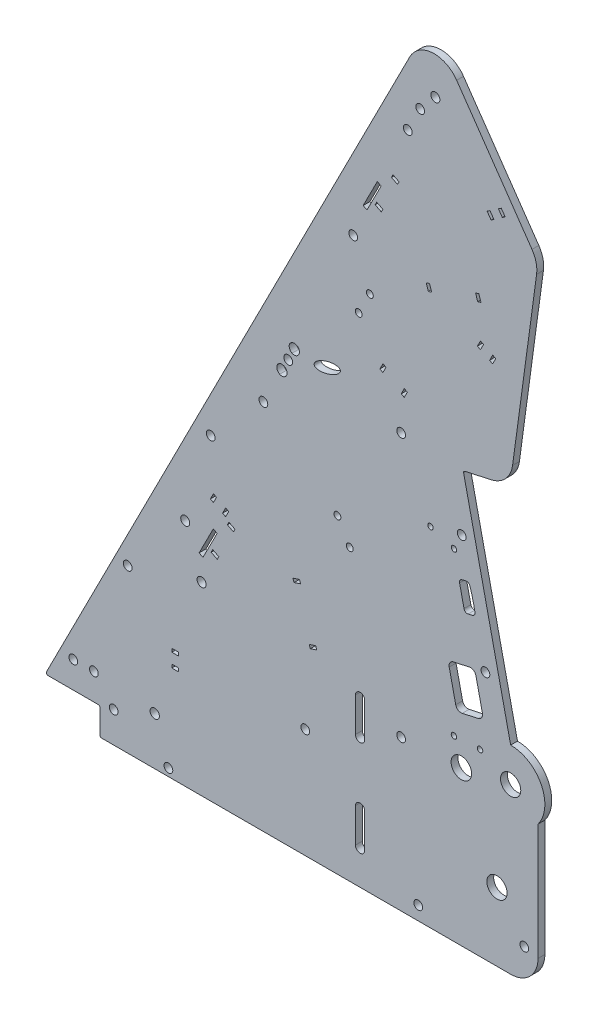
SolidWorks part; units mm, degrees
other "Markup1"
sketch "Sketch5"
ref_plane "Front Plane" through (0, 0, 0) normal (0, 0, 1) x (1, 0, 0)
ref_plane "Top Plane" through (0, 0, 0) normal (0, 1, 0) x (1, 0, 0)
ref_plane "Right Plane" through (0, 0, 0) normal (1, 0, 0) x (0, 0, -1)
sketch "Sketch1" plane through (0, 0, 0) normal (0, 0, 1) x (1, 0, 0)
  line L1 (228.6, -12.7) -> (228.6, 53.975)
  line L2 (178.7547, 351.4131) -> (0, 0)
  line L3 (228.6, 279.4) -> (178.7547, 351.4131)
  line L5 (0, 0) -> (25.4, 0)
  line L6 (25.4, 0) -> (25.4, -12.7)
  line L7 (25.4, -12.7) -> (228.6, -12.7)
  line L9 (215.9, 79.375) -> (193.9097, 178.5667)
  line L10 (193.9097, 178.5667) -> (215.6079, 183.377)
  line L11 (215.6079, 183.377) -> (228.6, 279.4)
  arc A0 (228.6, 53.975) -> (215.9, 79.375) centre (215.9, 63.5) ccw
  dimension "D7" = 12.7
  dimension "D8" = 76.2
  dimension "D10" = 31.75
  dimension "D2" = 292.1
  dimension "D3" = 25.4
  dimension "D4" = 215.9
  dimension "D5" = 394.2644
  dimension "D6" = 203.2
  dimension "D9" = 63.039
  dimension "D11" = 101.6
  dimension "D12" = 12.5
  dimension "D13" = 22.225
extrude "Boss-Extrude1" add sketch "Sketch1" along normal blind 3.175
sketch "Sketch2" plane through (0, 0, 3.175) normal (0, 0, 1) x (1, 0, 0)
  line L0 (178.7547, 351.4131) -> (0, 0) construction
  line L1 (25.4, -12.7) -> (228.6, -12.7) construction
  line L2 (215.9, 79.375) -> (193.9097, 178.5667) construction
  line L3 (193.9097, 178.5667) -> (215.6079, 183.377) construction
  line L4 (215.9, 79.375) -> (193.9097, 178.5667) construction
  line L5 (64.9432, 94.0578) -> (72.5445, 73.1732) construction
  line L6 (64.9432, 94.0578) -> (89.8317, 94.0578) construction
  line L10 (228.6, -12.7) -> (228.6, 53.975) construction
  circle A0 centre (64.9432, 94.0578) radius 2.0955
  circle A1 centre (180.975, 322.1643) radius 2.0955
  circle A2 centre (72.5445, 73.1732) radius 2.0955
  circle A3 centre (193.2078, 152.3944) radius 2.032
  circle A4 centre (215.9, 63.5) radius 4.699
  circle A7 centre (173.0375, -6.35) radius 2.032
  circle A8 centre (204.203, 102.7985) radius 2.032
  circle A26 centre (209.55, 19.05) radius 4.699
  arc A30 (228.6, 53.975) -> (215.9, 79.375) centre (215.9, 63.5) ccw construction
  circle A31 centre (165.1, 179.3875) radius 2.032
  dimension "D3" = 4.191
  dimension "D5" = 4.191
  dimension "D9" = 4.191
  dimension "D20" = 9.398
  dimension "D23" = 9.398
  dimension "D18" = 4.064
  dimension "D26" = 4.064
  dimension "D14" = 4.064
  dimension "D2" = 15.24
  dimension "D6" = 15.24
  dimension "D7" = 22.225
  dimension "D21" = 44.45
  dimension "D22" = 6.35
  dimension "D19" = 160.3375
  dimension "D24" = 44.45
  dimension "D25" = 6.35
  dimension "D27" = 25.4
  dimension "D28" = 50.8
  dimension "D29" = 6.35
  dimension "D17" = 6.35
  dimension "D33" = 55.5625
  dimension "D15" = 114.3
  dimension "D4" = 180.975
  dimension "D8" = 70
extrude "Cut-Extrude1" cut sketch "Sketch2" against normal through all
sketch "Sketch7" plane through (0, 0, 3.175) normal (0, 0, 1) x (1, 0, 0)
  line L0 (146.05, 3.175) -> (146.05, 19.05) construction
  line L1 (143.891, 3.175) -> (143.891, 19.05)
  line L2 (148.209, 3.175) -> (148.209, 19.05)
  line L3 (146.05, 47.625) -> (146.05, 63.5) construction
  line L4 (143.891, 47.625) -> (143.891, 63.5)
  line L5 (148.209, 47.625) -> (148.209, 63.5)
  line L6 (25.4, -12.7) -> (228.6, -12.7) construction
  line L12 (228.6, -12.7) -> (228.6, 53.975) construction
  line L13 (25.4, -12.7) -> (228.6, -12.7) construction
  arc A0 (143.891, 3.175) -> (148.209, 3.175) centre (146.05, 3.175) ccw
  arc A1 (148.209, 19.05) -> (143.891, 19.05) centre (146.05, 19.05) ccw
  arc A2 (143.891, 47.625) -> (148.209, 47.625) centre (146.05, 47.625) ccw
  arc A3 (148.209, 63.5) -> (143.891, 63.5) centre (146.05, 63.5) ccw
  circle A8 centre (50.8, 9.525) radius 2.159
  point P2 (146.05, 11.1125)
  point P9 (146.05, 55.5625)
  dimension "D1" = 4.318
  dimension "D5" = 4.318
  dimension "D2" = 15.875
  dimension "D3" = 15.875
  dimension "D4" = 44.45
  dimension "D6" = 95.25
  dimension "D7" = 82.55
  dimension "D8" = 15.875
  dimension "D9" = 22.225
extrude "Cut-Extrude2" cut sketch "Sketch7" against normal through all
sketch "Sketch10" plane through (0, 0, 3.175) normal (0, 0, 1) x (1, 0, 0)
  circle A1 centre (165.1, 57.15) radius 2.032
  circle A2 centre (120.65, 38.1) radius 2.032
  circle A3 centre (13.0465, 12.3347) radius 2.032
  circle A4 centre (22.5715, 12.3347) radius 2.032
  circle A5 centre (38.2611, 62.6146) radius 2.032
  dimension "D1" = 4.064
  dimension "D2" = 4.064
  dimension "D4" = 63.5
  dimension "D5" = 69.85
extrude "Cut-Extrude3" cut sketch "Sketch10" against normal up to next
fillet "Fillet1" radius 12.7 4 edges at (228.6, -12.7, 1.5875) (178.7547, 351.4131, 1.5875) (215.6079, 183.377, 1.5875) (228.6, 279.4, 1.5875)
fillet "Fillet2" radius 0.7937 4 edges at (25.4, -12.7, 1.5875) (25.4, 0, 1.5875) (193.9097, 178.5667, 1.5875) (0, 0, 1.5875)
sketch "Sketch12" plane through (0, 0, 3.175) normal (0, 0, 1) x (1, 0, 0)
  circle A0 centre (31.75, 1.5875) radius 2.032
  circle A1 centre (222.25, 1.5875) radius 2.032
  circle A2 centre (57.15, -9.2075) radius 2.032
  circle A3 centre (57.15, -9.2075) radius 2.286 construction
  dimension "D1" = 4.064
  dimension "D2" = 4.064
extrude "Cut-Extrude5" cut sketch "Sketch12" against normal through all
sketch "Sketch13" plane through (0, 0, 3.175) normal (0, 0, 1) x (1, 0, 0)
  line L2 (194.6847, 178.7385) -> (206.9592, 181.4597) construction
  line L5 (199.2434, 101.699) -> (189.6226, 145.0954) construction
  line L6 (189.6022, 69.9806) -> (201.7089, 70.5092) construction
  line L7 (186.8444, 98.9502) -> (199.2434, 101.699)
  line L8 (186.8444, 98.9502) -> (190.9676, 80.3518)
  line L9 (190.9676, 80.3518) -> (203.3665, 83.1006)
  line L10 (199.2434, 101.699) -> (203.3665, 83.1006)
  line L11 (189.6022, 69.9806) -> (190.9676, 80.3518) construction
  line L12 (201.7089, 70.5092) -> (203.3665, 83.1006) construction
  line L13 (215.9, 79.375) -> (194.0815, 177.7917) construction
  line L14 (178.7216, 148.5324) -> (189.6226, 145.0954) construction
  line L15 (195.1281, 134.9336) -> (193.4153, 134.5539)
  line L16 (192.209, 132.6604) -> (194.2706, 123.3612)
  line L17 (196.1641, 122.1549) -> (198.1091, 122.5861)
  line L18 (211.4332, 99.5233) -> (205.2337, 98.1489) construction
  line L19 (198.3765, 158.4184) -> (211.4332, 99.5233) construction
  circle A0 centre (189.6022, 69.9806) radius 1.27
  circle A1 centre (201.7089, 70.5092) radius 1.27
  circle A2 centre (178.7216, 148.5324) radius 1.27
  circle A3 centre (189.6226, 145.0954) radius 1.27
  arc A4 (199.3306, 124.402) -> (196.9796, 133.88) centre (134.9024, 113.4517) ccw
  arc A6 (199.4957, 103.5221) -> (189.2475, 149.7492) centre (134.9024, 113.4517) ccw construction
  arc A7 (195.1281, 134.9336) -> (196.9796, 133.88) centre (195.4717, 133.3837) cw
  arc A8 (198.1091, 122.5861) -> (199.3306, 124.402) centre (197.7655, 124.136) ccw
  arc A9 (194.2706, 123.3612) -> (196.1641, 122.1549) centre (195.8205, 123.7048) ccw
  arc A10 (193.4153, 134.5539) -> (192.209, 132.6604) centre (193.7589, 133.004) ccw
  point P26 (208.3335, 98.8361)
  point P31 (196.515, 135.2411)
  point P36 (194.6142, 121.8113)
  point P39 (191.8654, 134.2103)
  dimension "D7" = 2.54
  dimension "D16" = 1.5875
  dimension "D2" = 11.43
  dimension "D3" = 76.2
  dimension "D4" = 12.7
  dimension "D5" = 19.05
  dimension "D6" = 120
  dimension "D8" = 110
  dimension "D9" = 80
  dimension "D10" = 12.7
  dimension "D11" = 44.45
  dimension "D12" = 11.43
  dimension "D13" = 12.7
  dimension "D14" = 4.7625
  dimension "D15" = 38.1
extrude "Cut-Extrude6" cut sketch "Sketch13" against normal through all both and the other way through all
sketch "Sketch14" plane through (0, 0, 3.175) normal (0, 0, 1) x (1, 0, 0)
  line L0 (26.1937, -12.7) -> (215.9, -12.7) construction
  line L1 (228.6, 0) -> (228.6, 53.975) construction
  line L2 (112.7125, 182.5625) -> (101.1964, 159.9231) construction
  line L3 (169.1053, 332.4434) -> (0.5868, 1.1536) construction
  line L4 (112.7125, 182.5625) -> (136.864, 190.4279) construction
  line L5 (147.4827, 261.9243) -> (154.0469, 274.8287)
  line L6 (147.4827, 261.9243) -> (149.2654, 261.0175)
  line L7 (154.0469, 274.8287) -> (155.8295, 273.922)
  line L8 (149.2654, 261.0175) -> (155.8295, 273.922)
  line L9 (169.1053, 332.4434) -> (0.5868, 1.1536) construction
  line L10 (160.5905, 279.7801) -> (161.3102, 281.1951)
  line L11 (160.5905, 279.7801) -> (163.4204, 278.3406)
  line L12 (161.3102, 281.1951) -> (164.1402, 279.7556)
  line L13 (163.4204, 278.3406) -> (164.1402, 279.7556)
  line L14 (153.7897, 266.4104) -> (156.6196, 264.9709)
  line L15 (153.7897, 266.4104) -> (153.0699, 264.9954)
  line L16 (156.6196, 264.9709) -> (155.8998, 263.5559)
  line L17 (153.0699, 264.9954) -> (155.8998, 263.5559)
  line L19 (178.2697, 245.9923) -> (179.2404, 242.9693)
  line L20 (178.2697, 245.9923) -> (176.7582, 245.5069)
  line L21 (179.2404, 242.9693) -> (177.7289, 242.4839)
  line L22 (176.7582, 245.5069) -> (177.7289, 242.4839)
  line L24 (200.6096, 249.8308) -> (199.639, 252.8538)
  line L25 (200.6096, 249.8308) -> (202.1211, 250.3161)
  line L26 (199.639, 252.8538) -> (201.1505, 253.3391)
  line L27 (202.1211, 250.3161) -> (201.1505, 253.3391)
  line L34 (77.9534, 97.2255) -> (79.736, 96.3187)
  line L47 (77.9534, 97.2255) -> (71.3892, 84.3211)
  line L56 (79.736, 96.3187) -> (73.1718, 83.4143)
  line L57 (71.3892, 84.3211) -> (73.1718, 83.4143)
  line L58 (85.2167, 103.5918) -> (84.497, 102.1769)
  line L59 (85.2167, 103.5918) -> (88.0466, 102.1523)
  line L60 (84.497, 102.1769) -> (87.3269, 100.7374)
  line L61 (88.0466, 102.1523) -> (87.3269, 100.7374)
  line L62 (156.643, 199.3999) -> (158.0826, 202.2298)
  line L63 (156.643, 199.3999) -> (155.2281, 200.1197)
  line L64 (158.0826, 202.2298) -> (156.6676, 202.9496)
  line L65 (155.2281, 200.1197) -> (156.6676, 202.9496)
  line L66 (165.1328, 195.0814) -> (166.5723, 197.9113)
  line L67 (165.1328, 195.0814) -> (166.5478, 194.3617)
  line L68 (166.5723, 197.9113) -> (167.9873, 197.1916)
  line L69 (166.5478, 194.3617) -> (167.9873, 197.1916)
  line L78 (77.6961, 88.8072) -> (76.9764, 87.3922)
  line L79 (201.9154, 234.7497) -> (200.4759, 231.9198)
  line L80 (201.9154, 234.7497) -> (203.3303, 234.0299)
  line L81 (200.4759, 231.9198) -> (201.8908, 231.2)
  line L82 (203.3303, 234.0299) -> (201.8908, 231.2)
  line L83 (206.1357, 229.0407) -> (207.5752, 231.8707)
  line L84 (206.1357, 229.0407) -> (207.5507, 228.321)
  line L85 (207.5752, 231.8707) -> (208.9902, 231.1509)
  line L86 (207.5507, 228.321) -> (208.9902, 231.1509)
  line L88 (205.014, 288.3715) -> (206.821, 285.7609)
  line L89 (205.014, 288.3715) -> (206.3193, 289.275)
  line L90 (206.821, 285.7609) -> (208.1263, 286.6644)
  line L91 (206.3193, 289.275) -> (208.1263, 286.6644)
  line L92 (210.2352, 291.9855) -> (212.0422, 289.3749)
  line L93 (210.2352, 291.9855) -> (211.5405, 292.889)
  line L94 (212.0422, 289.3749) -> (213.3475, 290.2784)
  line L95 (211.5405, 292.889) -> (213.3475, 290.2784)
  line L96 (225.7968, 283.4499) -> (190.8675, 333.9133) construction
  line L97 (77.6961, 88.8072) -> (80.5261, 87.3677)
  line L98 (76.9764, 87.3922) -> (79.8063, 85.9527)
  line L99 (80.5261, 87.3677) -> (79.8063, 85.9527)
  line L100 (122.4534, 73.1037) -> (122.9512, 71.5963)
  line L101 (122.4534, 73.1037) -> (125.4682, 74.0993)
  line L102 (122.9512, 71.5963) -> (125.9661, 72.5919)
  line L103 (125.4682, 74.0993) -> (125.9661, 72.5919)
  line L104 (114.9173, 95.9228) -> (115.4151, 94.4154)
  line L105 (114.9173, 95.9228) -> (117.9322, 96.9185)
  line L106 (115.4151, 94.4154) -> (118.43, 95.411)
  line L107 (117.9322, 96.9185) -> (118.43, 95.411)
  line L108 (73.3338, 88.1438) -> (77.899, 97.1186) construction
  line L109 (75.1164, 87.2371) -> (79.6816, 96.2118) construction
  line L110 (76.2812, 89.5269) -> (86.5313, 84.313) construction
  line L111 (83.082, 102.8966) -> (93.3321, 97.6827) construction
  line L112 (121.934, 72.0825) -> (123.4755, 75.113) construction
  line L113 (127.9171, 72.8537) -> (123.4755, 75.113) construction
  line L114 (112.3753, 83.5081) -> (119.5388, 97.5909) construction
  line L115 (112.1491, 96.0767) -> (117.4079, 93.4017) construction
  line L116 (149.0052, 264.9173) -> (147.5544, 262.0651) construction
  line L117 (150.7878, 264.0106) -> (151.2099, 264.8403) construction
  line L118 (162.6248, 261.9162) -> (152.3747, 267.1302) construction
  line L119 (169.4256, 275.2859) -> (159.1755, 280.4999) construction
  line L120 (199.3876, 252.3597) -> (200.1584, 253.8749) construction
  line L121 (198.6169, 250.8445) -> (203.0585, 248.5852) construction
  line L122 (203.2698, 247.9167) -> (195.3067, 232.262) construction
  line L123 (180.2625, 244.9786) -> (175.0037, 247.6536) construction
  line L124 (178.1316, 240.7894) -> (185.2951, 254.8722) construction
  line L125 (190.7763, 226.1672) -> (185.5176, 228.8422) construction
  line L126 (58.7375, 39.6875) -> (61.9125, 39.6875)
  line L127 (58.7375, 39.6875) -> (58.7375, 38.1)
  line L128 (61.9125, 39.6875) -> (61.9125, 38.1)
  line L129 (58.7375, 38.1) -> (61.9125, 38.1)
  line L130 (58.7375, 33.3375) -> (61.9125, 33.3375)
  line L131 (58.7375, 33.3375) -> (58.7375, 31.75)
  line L132 (61.9125, 33.3375) -> (61.9125, 31.75)
  line L133 (58.7375, 31.75) -> (61.9125, 31.75)
  line L135 (78.0516, 111.4242) -> (76.6121, 108.5943)
  line L136 (78.0516, 111.4242) -> (79.4665, 110.7045)
  line L137 (76.6121, 108.5943) -> (78.027, 107.8745)
  line L138 (79.4665, 110.7045) -> (78.027, 107.8745)
  line L139 (82.2719, 105.7153) -> (83.7114, 108.5452)
  line L140 (82.2719, 105.7153) -> (83.6869, 104.9955)
  line L141 (83.7114, 108.5452) -> (85.1264, 107.8254)
  line L142 (83.6869, 104.9955) -> (85.1264, 107.8254)
  circle A0 centre (142.875, 247.65) radius 2.032
  circle A1 centre (112.7125, 182.5625) radius 2.032
  circle A2 centre (101.1964, 159.9231) radius 2.032
  circle A3 centre (150.594, 227.8985) radius 1.6 construction
  circle A4 centre (145.4254, 217.7376) radius 1.6 construction
  circle A5 centre (135.5457, 131.3585) radius 1.6 construction
  circle A6 centre (141.2457, 121.4859) radius 1.6 construction
  circle A7 centre (150.594, 227.8985) radius 1.6
  circle A8 centre (145.4254, 217.7376) radius 1.6
  circle A9 centre (135.5457, 131.3585) radius 1.6
  circle A10 centre (141.2457, 121.4859) radius 1.6
  arc A13 (0, 1.5875) -> (1.5875, 0) centre (1.5875, 1.5875) ccw construction
  ellipse E0 centre (109.8335, 176.9027) end of major axis (108.7539, 174.7802) minor radius 2.32 (108.7539, 174.7802) -> (110.9131, 179.0251) ccw construction
  ellipse E1 centre (109.8335, 176.9027) end of major axis (108.7539, 174.7802) minor radius 2.32 (108.7539, 174.7802) -> (110.9131, 179.0251) ccw
  ellipse E2 centre (130.8261, 188.4615) end of major axis (124.7883, 186.4952) minor radius 2.3812
  ellipse E3 centre (115.5915, 188.2223) end of major axis (114.5119, 186.0999) minor radius 2.32 (114.5119, 186.0999) -> (116.6711, 190.3448) ccw construction
  ellipse E4 centre (115.5915, 188.2223) end of major axis (114.5119, 186.0999) minor radius 2.32 (114.5119, 186.0999) -> (116.6711, 190.3448) ccw
  spline S0 degree 3 poles (603.8918, 1049.0657) (-166.9189, -675.3083) (147.8077, 168.3802) (110.3225, 179.2425) (110.1654, 179.2721) (109.6955, 179.3152) (109.3734, 179.2831) (108.9218, 179.1456) (108.7737, 179.0841) (108.4954, 178.9343) (108.365, 178.8464) (108.1219, 178.6442) (108.0097, 178.5297) (107.8134, 178.2839) (107.7278, 178.1512) (107.5834, 177.8672) (107.527, 177.7202) (107.4441, 177.4168) (107.4178, 177.2585) (107.3978, 176.9432) (107.4036, 176.7863) (107.4465, 176.4736) (107.4841, 176.3175) (107.5874, 176.0205) (107.6532, 175.8777) (107.8133, 175.6037) (107.9066, 175.4748) (114.8282, 167.6036) (173.9427, 200.577) (-567.4982, 911.3293) knots -15.287416 -15.287416 -15.287416 -15.287416 0.0625 0.0625 0.125 0.125 0.25 0.25 0.3125 0.3125 0.375 0.375 0.4375 0.4375 0.5 0.5 0.5625 0.5625 0.625 0.625 0.6875 0.6875 0.75 0.75 0.8125 0.8125 0.875 0.875 4.983329 4.983329 4.983329 4.983329 only from (110.9131, 179.0251) to (108.7539, 174.7802) construction
  spline S1 degree 3 poles (110.9131, 179.0251) (110.7727, 179.0965) (110.6265, 179.1544) (110.3225, 179.2425) (110.1654, 179.2721) (109.6955, 179.3152) (109.3734, 179.2831) (108.9218, 179.1456) (108.7737, 179.0841) (108.4954, 178.9343) (108.365, 178.8464) (108.1219, 178.6442) (108.0097, 178.5297) (107.8134, 178.2839) (107.7278, 178.1512) (107.5834, 177.8672) (107.527, 177.7202) (107.4441, 177.4168) (107.4178, 177.2585) (107.3978, 176.9432) (107.4036, 176.7863) (107.4465, 176.4736) (107.4841, 176.3175) (107.5874, 176.0205) (107.6532, 175.8777) (107.8133, 175.6037) (107.9066, 175.4748) (108.2178, 175.121) (108.4736, 174.9228) (108.7539, 174.7802) knots 0 0 0 0 0.0625 0.0625 0.125 0.125 0.25 0.25 0.3125 0.3125 0.375 0.375 0.4375 0.4375 0.5 0.5 0.5625 0.5625 0.625 0.625 0.6875 0.6875 0.75 0.75 0.8125 0.8125 0.875 0.875 1 1 1 1
  spline S2 degree 3 poles (-635.3332, 847.705) (160.0375, 206.8561) (120.8424, 181.1302) (113.9875, 186.4501) (113.8729, 186.5577) (113.5583, 186.9155) (113.3974, 187.1901) (113.2413, 187.6401) (113.2046, 187.793) (113.1618, 188.1044) (113.1558, 188.2648) (113.176, 188.5797) (113.2018, 188.7347) (113.2848, 189.0394) (113.3426, 189.1891) (113.5563, 189.6095) (113.7586, 189.8627) (114.1212, 190.1647) (114.2542, 190.2544) (114.5324, 190.4041) (114.6775, 190.4645) (114.9798, 190.5567) (115.1369, 190.5882) (115.4499, 190.6199) (115.6074, 190.6207) (115.9244, 190.5918) (116.0795, 190.5623) (125.0451, 187.9725) (125.4505, 134.6135) (-868.6048, 361.2821) knots -3.325634 -3.325634 -3.325634 -3.325634 0.0625 0.0625 0.125 0.125 0.25 0.25 0.3125 0.3125 0.375 0.375 0.4375 0.4375 0.5 0.5 0.625 0.625 0.6875 0.6875 0.75 0.75 0.8125 0.8125 0.875 0.875 0.9375 0.9375 4.586013 4.586013 4.586013 4.586013 only from (114.5119, 186.0999) to (116.6711, 190.3448) construction
  spline S3 degree 3 poles (114.5119, 186.0999) (114.3711, 186.1715) (114.2359, 186.2574) (113.9875, 186.4501) (113.8729, 186.5577) (113.5583, 186.9155) (113.3974, 187.1901) (113.2413, 187.6401) (113.2046, 187.793) (113.1618, 188.1044) (113.1558, 188.2648) (113.176, 188.5797) (113.2018, 188.7347) (113.2848, 189.0394) (113.3426, 189.1891) (113.5563, 189.6095) (113.7586, 189.8627) (114.1212, 190.1647) (114.2542, 190.2544) (114.5324, 190.4041) (114.6775, 190.4645) (114.9798, 190.5567) (115.1369, 190.5882) (115.4499, 190.6199) (115.6074, 190.6207) (115.9244, 190.5918) (116.0795, 190.5623) (116.3815, 190.4751) (116.53, 190.4166) (116.6711, 190.3448) knots 0 0 0 0 0.0625 0.0625 0.125 0.125 0.25 0.25 0.3125 0.3125 0.375 0.375 0.4375 0.4375 0.5 0.5 0.625 0.625 0.6875 0.6875 0.75 0.75 0.8125 0.8125 0.875 0.875 0.9375 0.9375 1 1 1 1
  point P179 (82.9794, 105.3554)
  dimension "D1" = 4.064
  dimension "D15" = 3.175
  dimension "D2" = 195.2625
  dimension "D3" = 115.8875
  dimension "D4" = 85.725
  dimension "D5" = 260.35
  dimension "D6" = 25.4
  dimension "D7" = 4.7625
  dimension "D8" = 12.7
  dimension "D9" = 19.05
  dimension "D10" = 45
  dimension "D11" = 6.858
  dimension "D12" = 7.62
  dimension "D13" = 3.175
  dimension "D14" = 1.5875
  dimension "D16" = 1.5875
  dimension "D17" = 1.5875
  dimension "D18" = 9.525
  dimension "D19" = 47.625
  dimension "D20" = 38.1
  dimension "D21" = 6.858
  dimension "D22" = 7.62
  dimension "D23" = 1.5875
  dimension "D24" = 3.175
  dimension "D25" = 1.5875
  dimension "D26" = 4.7625
  dimension "D27" = 4.7625
  dimension "D28" = 1.5875
  dimension "D29" = 3.175
  dimension "D30" = 9.525
  dimension "D31" = 4.7625
  dimension "D32" = 4.7625
  dimension "D33" = 1.5875
  dimension "D34" = 3.175
  dimension "D35" = 6.35
  dimension "D36" = 12.7
  dimension "D37" = 1.5875
  dimension "D38" = 3.175
  dimension "D39" = 9.525
  dimension "D40" = 57.15
  dimension "D41" = 44.45
  dimension "D42" = 1.5875
  dimension "D43" = 4.7625
  dimension "D44" = 3.175
extrude "Cut-Extrude7" cut sketch "Sketch14" against normal through all
sketch "Sketch15" plane through (0, 0, 3.175) normal (0, 0, 1) x (1, 0, 0)
  line L0 (169.1053, 332.4434) -> (0.5868, 1.1536) construction
  circle A0 centre (76.7868, 134.1481) radius 2.032
  circle A1 centre (173.9472, 313.9507) radius 2.032
  circle A2 centre (168.1892, 302.631) radius 2.032
  circle A3 centre (173.9472, 313.9507) radius 1.905 construction
  circle A4 centre (168.1892, 302.631) radius 1.905 construction
  dimension "D1" = 4.064
  dimension "D4" = 4.064
  dimension "D2" = 7.62
  dimension "D3" = 76.2
extrude "Cut-Extrude8" cut sketch "Sketch15" against normal through all
fillet "Fillet3" radius 2.54 4 edges at (199.2434, 101.699, 1.5875) (186.8444, 98.9502, 1.5875) (190.9676, 80.3518, 1.5875) (203.3665, 83.1006, 1.5875)
sketch "Sketch16" plane through (0, 0, 3.175) normal (0, 0, 1) x (1, 0, 0)
  line L0 (228.6, 0) -> (228.6, 53.975) construction
  line L1 (26.1937, -12.7) -> (215.9, -12.7) construction
  circle A0 centre (193.04, 58.801) radius 4.7625
  dimension "D1" = 9.525
  dimension "D2" = 35.56
  dimension "D3" = 71.501
extrude "Cut-Extrude9" cut sketch "Sketch16" against normal through all
equation "\"D6@Sketch2\"=\"D2@Sketch2\""
